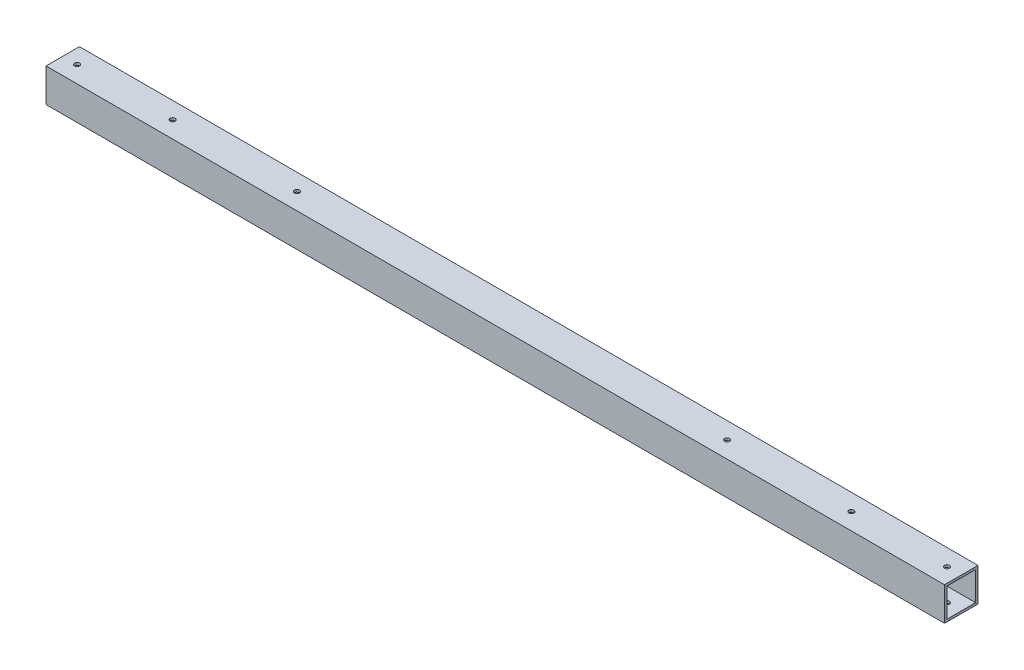
SolidWorks part; units mm, degrees
material "6061 Alloy"
ref_plane "Front Plane" through (0, 0, 0) normal (0, 0, 1) x (1, 0, 0)
ref_plane "Top Plane" through (0, 0, 0) normal (0, 1, 0) x (1, 0, 0)
ref_plane "Right Plane" through (0, 0, 0) normal (1, 0, 0) x (0, 0, -1)
sketch "Sketch1" plane through (0, 0, 0) normal (1, 0, 0) x (0, 0, -1)
  line L0 (-19.05, -19.05) -> (19.05, -19.05)
  line L1 (-22.225, -22.225) -> (22.225, -22.225)
  line L2 (-22.225, -22.225) -> (-22.225, 22.225)
  line L3 (-22.225, 22.225) -> (22.225, 22.225)
  line L4 (22.225, -22.225) -> (22.225, 22.225)
  line L5 (-22.225, -22.225) -> (22.225, 22.225) construction
  line L6 (-22.225, 22.225) -> (22.225, -22.225) construction
  line L7 (19.05, -19.05) -> (19.05, 19.05)
  line L8 (-19.05, 19.05) -> (19.05, 19.05)
  line L9 (-19.05, -19.05) -> (-19.05, 19.05)
  point P0 (0, 0)
  dimension "D1" = 44.45
  dimension "D2" = 3.175
extrude "Boss-Extrude1" add sketch "Sketch1" along normal blind 1193.8
hole_wizard "1/4 Clearance Hole1" positions "Sketch2" profile "Sketch3" hole size "1/4" standard "ANSI Inch" end condition through all
sketch "Sketch2" plane through (0, 22.225, 0) normal (0, 1, 0) x (1, 0, 0)
  line L0 (596.9, -22.225) -> (596.9, 22.225) construction
  line L1 (1193.8, -22.225) -> (0, -22.225) construction
  line L2 (1193.8, 22.225) -> (0, 22.225) construction
  line L3 (0, 0) -> (1193.8, 0) construction
  line L4 (1193.8, 22.225) -> (1193.8, -22.225) construction
  line L5 (0, 22.225) -> (0, -22.225) construction
  point P0 (311.15, 0)
  point P2 (146.05, 0)
  point P4 (19.05, 0)
  point P14 (1174.75, 0)
  point P15 (1047.75, 0)
  point P16 (882.65, 0)
  dimension "D1" = 571.5
  dimension "D2" = 146.05
  dimension "D3" = 19.05
sketch "Sketch3" plane through (311.15, 22.225, 0) normal (1, 0, 0) x (0, 0, 1)
  line L0 (0, 0) -> (0, 44.45)
  line L1 (0, 44.45) -> (3.3782, 44.45)
  line L2 (3.3782, 44.45) -> (3.3782, 0)
  line L5 (3.3782, 0) -> (0, 0)
  line L11 (0, -6.35) -> (0, 107.95) construction
  dimension "Thru Hole Dia." = 6.7564
  dimension "Thru Hole Depth" = 44.45
